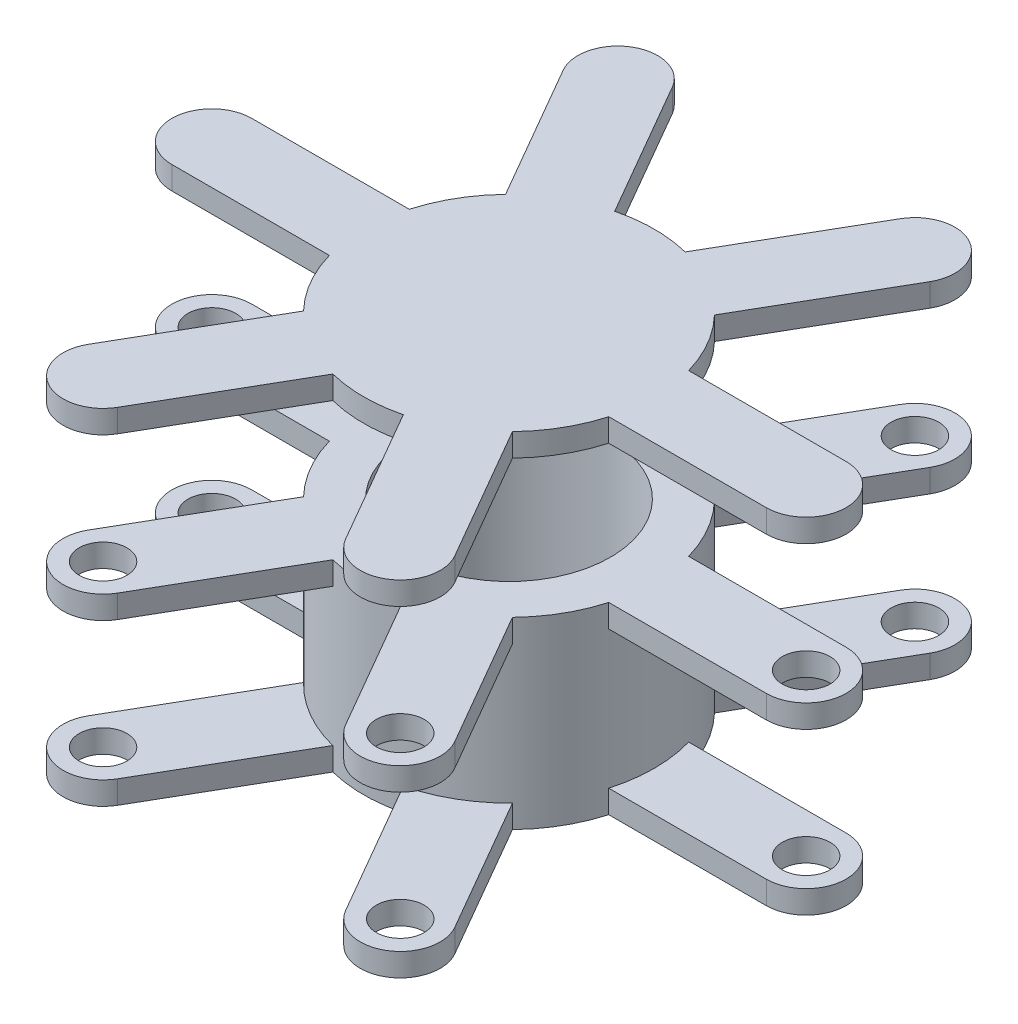
SolidWorks part; units mm, degrees
ref_plane "Front Plane" through (0, 0, 0) normal (0, 0, 1) x (1, 0, 0)
ref_plane "Top Plane" through (0, 0, 0) normal (0, 1, 0) x (1, 0, 0)
ref_plane "Right Plane" through (0, 0, 0) normal (1, 0, 0) x (0, 0, -1)
sketch "Sketch1" plane through (0, 0, 0) normal (0, 1, 0) x (1, 0, 0)
  line L0 (60.7918, 17.388) -> (129.3149, 17.388)
  line L1 (129.5014, -17.387) -> (60.7921, -17.387)
  line L2 (45.4544, -43.9532) -> (79.7159, -103.296)
  line L3 (49.6931, -120.845) -> (15.3384, -61.341)
  line L4 (-15.3374, -61.3413) -> (-49.599, -120.684)
  line L5 (-79.8083, -103.458) -> (-45.4537, -43.954)
  line L6 (-60.7918, -17.388) -> (-129.3149, -17.388)
  line L7 (-129.5014, 17.387) -> (-60.7921, 17.387)
  line L8 (-45.4544, 43.9532) -> (-79.7159, 103.296)
  line L9 (-49.6931, 120.845) -> (-15.3384, 61.341)
  line L10 (15.3374, 61.3413) -> (49.599, 120.684)
  line L11 (79.8083, 103.458) -> (45.4537, 43.954)
  circle A0 centre (0, 0) radius 63.2296
  circle A1 centre (0, 0) radius 44.1465
  arc A2 (129.3149, 17.388) -> (129.5014, -17.387) centre (129.3149, 0) cw
  circle A3 centre (129.3149, 0) radius 10.3928
  circle A4 centre (0, 0) radius 63.2296
  arc A5 (79.7159, -103.296) -> (49.6931, -120.845) centre (64.6575, -111.99) cw
  circle A6 centre (64.6575, -111.99) radius 10.3928
  circle A7 centre (0, 0) radius 63.2296
  arc A8 (-49.599, -120.684) -> (-79.8083, -103.458) centre (-64.6575, -111.99) cw
  circle A9 centre (-64.6575, -111.99) radius 10.3928
  circle A10 centre (0, 0) radius 63.2296
  arc A11 (-129.3149, -17.388) -> (-129.5014, 17.387) centre (-129.3149, 0) cw
  circle A12 centre (-129.3149, 0) radius 10.3928
  circle A13 centre (0, 0) radius 63.2296
  arc A14 (-79.7159, 103.296) -> (-49.6931, 120.845) centre (-64.6575, 111.99) cw
  circle A15 centre (-64.6575, 111.99) radius 10.3928
  circle A16 centre (0, 0) radius 63.2296
  arc A17 (49.599, 120.684) -> (79.8083, 103.458) centre (64.6575, 111.99) cw
  circle A18 centre (64.6575, 111.99) radius 10.3928
  point P47 (0, 0)
extrude "Boss-Extrude1" add sketch "Sketch1" along normal blind 70 contours A0 A1 region at (60.8461, 0, -8.5307)
extrude "Boss-Extrude2" add sketch "Sketch1<3>" along normal blind 10 contours A8 L4 A0 L5 A9 | A11 L6 A0 L7 A12 | A14 L8 A0 L9 A15 | A17 L10 A0 L11 A18 | A2 L0 A0 L1 A3 | A5 L2 A0 L3 A6 region at (99.1314, 0, -0.0005) region at (49.5653, 0, -85.8505) region at (49.5661, 0, 85.8501) region at (-49.5661, 0, -85.8501) region at (-49.5653, 0, 85.8505) region at (-99.1314, 0, 0.0005)
sketch "Sketch1<3>" plane through (0, 0, 0) normal (0, 1, 0) x (1, 0, 0) same geometry as "Sketch1"
sketch "Sketch5" plane through (0, 70, 0) normal (0, 1, 0) x (1, 0, 0)
  line L0 (-129.3149, -17.388) -> (-60.7918, -17.388) construction
  line L1 (-60.7921, 17.387) -> (-129.5014, 17.387) construction
  line L2 (-79.7159, 103.296) -> (-45.4544, 43.9532)
  line L3 (-15.3384, 61.341) -> (-49.6931, 120.845)
  line L4 (-79.7159, 103.296) -> (-45.4544, 43.9532)
  line L5 (-15.3384, 61.341) -> (-49.6931, 120.845)
  line L6 (-49.599, -120.684) -> (-15.3374, -61.3413) construction
  line L7 (-45.4537, -43.954) -> (-79.8083, -103.458) construction
  line L8 (79.7159, -103.296) -> (45.4544, -43.9532) construction
  line L9 (15.3384, -61.341) -> (49.6931, -120.845) construction
  line L10 (129.3149, 17.388) -> (60.7918, 17.388) construction
  line L11 (60.7921, -17.387) -> (129.5014, -17.387) construction
  line L12 (49.599, 120.684) -> (15.3374, 61.3413) construction
  line L13 (45.4537, 43.954) -> (79.8083, 103.458) construction
  line L14 (-129.3149, -17.388) -> (-60.7918, -17.388)
  line L15 (-60.7921, 17.387) -> (-129.5014, 17.387)
  line L16 (-49.599, -120.684) -> (-15.3374, -61.3413)
  line L17 (-45.4537, -43.954) -> (-79.8083, -103.458)
  line L18 (79.7159, -103.296) -> (45.4544, -43.9532)
  line L19 (15.3384, -61.341) -> (49.6931, -120.845)
  line L20 (129.3149, 17.388) -> (60.7918, 17.388)
  line L21 (60.7921, -17.387) -> (129.5014, -17.387)
  line L22 (49.599, 120.684) -> (15.3374, 61.3413)
  line L23 (45.4537, 43.954) -> (79.8083, 103.458)
  arc A0 (-129.5014, 17.387) -> (-129.3149, -17.388) centre (-129.3149, 0) ccw construction
  circle A1 centre (0, 0) radius 63.2296
  circle A2 centre (0, 0) radius 63.2296
  arc A3 (-60.7921, 17.387) -> (-60.7918, -17.388) centre (0, 0) ccw construction
  arc A4 (-49.6931, 120.845) -> (-79.7159, 103.296) centre (-64.6575, 111.99) ccw
  arc A5 (-15.3384, 61.341) -> (-45.4544, 43.9532) centre (0, 0) ccw
  arc A6 (-49.6931, 120.845) -> (-79.7159, 103.296) centre (-64.6575, 111.99) ccw
  arc A7 (-15.3384, 61.341) -> (-45.4544, 43.9532) centre (0, 0) ccw
  arc A8 (-79.8083, -103.458) -> (-49.599, -120.684) centre (-64.6575, -111.99) ccw construction
  arc A9 (-45.4537, -43.954) -> (-15.3374, -61.3413) centre (0, 0) ccw construction
  arc A10 (49.6931, -120.845) -> (79.7159, -103.296) centre (64.6575, -111.99) ccw construction
  arc A11 (15.3384, -61.341) -> (45.4544, -43.9532) centre (0, 0) ccw construction
  arc A12 (129.5014, -17.387) -> (129.3149, 17.388) centre (129.3149, 0) ccw construction
  arc A13 (60.7921, -17.387) -> (60.7918, 17.388) centre (0, 0) ccw construction
  arc A14 (79.8083, 103.458) -> (49.599, 120.684) centre (64.6575, 111.99) ccw construction
  arc A15 (45.4537, 43.954) -> (15.3374, 61.3413) centre (0, 0) ccw construction
  arc A16 (-129.5014, 17.387) -> (-129.3149, -17.388) centre (-129.3149, 0) ccw
  arc A17 (-60.7921, 17.387) -> (-60.7918, -17.388) centre (0, 0) ccw
  arc A18 (-79.8083, -103.458) -> (-49.599, -120.684) centre (-64.6575, -111.99) ccw
  arc A19 (-45.4537, -43.954) -> (-15.3374, -61.3413) centre (0, 0) ccw
  arc A20 (49.6931, -120.845) -> (79.7159, -103.296) centre (64.6575, -111.99) ccw
  arc A21 (15.3384, -61.341) -> (45.4544, -43.9532) centre (0, 0) ccw
  arc A22 (129.5014, -17.387) -> (129.3149, 17.388) centre (129.3149, 0) ccw
  arc A23 (60.7921, -17.387) -> (60.7918, 17.388) centre (0, 0) ccw
  arc A24 (79.8083, 103.458) -> (49.599, 120.684) centre (64.6575, 111.99) ccw
  arc A25 (45.4537, 43.954) -> (15.3374, 61.3413) centre (0, 0) ccw
  circle A26 centre (64.6575, -111.99) radius 10.3928 construction
  circle A27 centre (129.3149, 0) radius 10.3928 construction
  circle A28 centre (64.6575, 111.99) radius 10.3928 construction
  circle A29 centre (-64.6575, 111.99) radius 10.3928 construction
  circle A30 centre (-129.3149, 0) radius 10.3928 construction
  circle A31 centre (-64.6575, -111.99) radius 10.3928 construction
  circle A32 centre (64.6575, -111.99) radius 10.3928
  circle A33 centre (129.3149, 0) radius 10.3928
  circle A34 centre (64.6575, 111.99) radius 10.3928
  circle A35 centre (-64.6575, 111.99) radius 10.3928
  circle A36 centre (-129.3149, 0) radius 10.3928
  circle A37 centre (-64.6575, -111.99) radius 10.3928
  circle M22 centre (0, 0) radius 44.1465
  circle M23 centre (0, 0) radius 63.2296
  dimension "D1" = 0
  dimension "D2" = 0
extrude "Boss-Extrude5" add sketch "Sketch5" along normal blind 10 contours M23 M22 | L23 A24 L22 A34 M23 | L21 A22 L20 A33 M23 | L19 A20 L18 A32 M23 | L17 A18 L16 A37 M23 | L15 A16 L14 A36 M23 | L5 A6 L4 A35 M23 region at (-49.5661, 70, -85.8501) region at (-30.7211, 70, -53.2094) region at (-99.1314, 70, 0.0005) region at (49.5653, 70, -85.8505) region at (-49.5653, 70, 85.8505) region at (99.1314, 70, -0.0005) region at (49.5661, 70, 85.8501)
ref_plane "Plane1" through (0, 140, 0) normal (0, 1, 0) x (1, 0, 0)
sketch "Sketch6" plane through (0, 140, 0) normal (0, 1, 0) x (1, 0, 0)
  line L12 (15.3384, -61.341) -> (49.6931, -120.845)
  line L13 (79.7159, -103.296) -> (45.4544, -43.9532)
  line L14 (60.7921, -17.387) -> (129.5014, -17.387)
  line L15 (129.3149, 17.388) -> (60.7918, 17.388)
  line L16 (45.4537, 43.954) -> (79.8083, 103.458)
  line L17 (49.599, 120.684) -> (15.3374, 61.3413)
  line L18 (-15.3384, 61.341) -> (-49.6931, 120.845)
  line L19 (-79.7159, 103.296) -> (-45.4544, 43.9532)
  line L20 (-60.7921, 17.387) -> (-129.5014, 17.387)
  line L21 (-129.3149, -17.388) -> (-60.7918, -17.388)
  line L22 (-45.4537, -43.954) -> (-79.8083, -103.458)
  line L23 (-49.599, -120.684) -> (-15.3374, -61.3413)
  line L24 (15.3384, -61.341) -> (49.6931, -120.845)
  line L25 (79.7159, -103.296) -> (45.4544, -43.9532)
  line L26 (60.7921, -17.387) -> (129.5014, -17.387)
  line L27 (129.3149, 17.388) -> (60.7918, 17.388)
  line L28 (45.4537, 43.954) -> (79.8083, 103.458)
  line L29 (49.599, 120.684) -> (15.3374, 61.3413)
  line L30 (-15.3384, 61.341) -> (-49.6931, 120.845)
  line L31 (-79.7159, 103.296) -> (-45.4544, 43.9532)
  line L32 (-60.7921, 17.387) -> (-129.5014, 17.387)
  line L33 (-129.3149, -17.388) -> (-60.7918, -17.388)
  line L34 (-45.4537, -43.954) -> (-79.8083, -103.458)
  line L35 (-49.599, -120.684) -> (-15.3374, -61.3413)
  arc A12 (-15.3374, -61.3413) -> (15.3384, -61.341) centre (0, 0) ccw
  arc A13 (49.6931, -120.845) -> (79.7159, -103.296) centre (64.6575, -111.99) ccw
  arc A14 (45.4544, -43.9532) -> (60.7921, -17.387) centre (0, 0) ccw
  arc A15 (129.5014, -17.387) -> (129.3149, 17.388) centre (129.3149, 0) ccw
  arc A16 (60.7918, 17.388) -> (45.4537, 43.954) centre (0, 0) ccw
  arc A17 (79.8083, 103.458) -> (49.599, 120.684) centre (64.6575, 111.99) ccw
  arc A18 (15.3374, 61.3413) -> (-15.3384, 61.341) centre (0, 0) ccw
  arc A19 (-49.6931, 120.845) -> (-79.7159, 103.296) centre (-64.6575, 111.99) ccw
  arc A20 (-45.4544, 43.9532) -> (-60.7921, 17.387) centre (0, 0) ccw
  arc A21 (-129.5014, 17.387) -> (-129.3149, -17.388) centre (-129.3149, 0) ccw
  arc A22 (-60.7918, -17.388) -> (-45.4537, -43.954) centre (0, 0) ccw
  arc A23 (-79.8083, -103.458) -> (-49.599, -120.684) centre (-64.6575, -111.99) ccw
  arc A24 (-15.3374, -61.3413) -> (15.3384, -61.341) centre (0, 0) ccw
  arc A25 (49.6931, -120.845) -> (79.7159, -103.296) centre (64.6575, -111.99) ccw
  arc A26 (45.4544, -43.9532) -> (60.7921, -17.387) centre (0, 0) ccw
  arc A27 (129.5014, -17.387) -> (129.3149, 17.388) centre (129.3149, 0) ccw
  arc A28 (60.7918, 17.388) -> (45.4537, 43.954) centre (0, 0) ccw
  arc A29 (79.8083, 103.458) -> (49.599, 120.684) centre (64.6575, 111.99) ccw
  arc A30 (15.3374, 61.3413) -> (-15.3384, 61.341) centre (0, 0) ccw
  arc A31 (-49.6931, 120.845) -> (-79.7159, 103.296) centre (-64.6575, 111.99) ccw
  arc A32 (-45.4544, 43.9532) -> (-60.7921, 17.387) centre (0, 0) ccw
  arc A33 (-129.5014, 17.387) -> (-129.3149, -17.388) centre (-129.3149, 0) ccw
  arc A34 (-60.7918, -17.388) -> (-45.4537, -43.954) centre (0, 0) ccw
  arc A35 (-79.8083, -103.458) -> (-49.599, -120.684) centre (-64.6575, -111.99) ccw
  dimension "D1" = 0
extrude "Boss-Extrude6" add sketch "Sketch6" along normal blind 10 separate body
